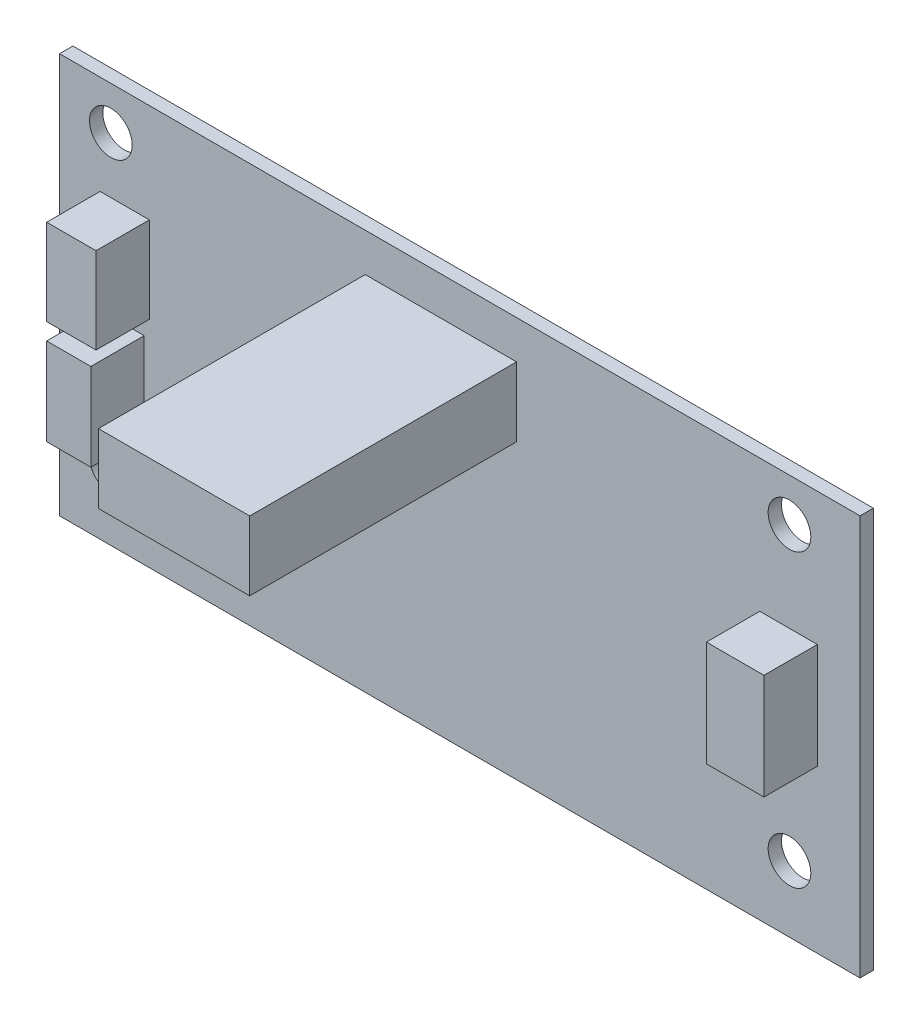
SolidWorks part; units mm, degrees
ref_plane "前视基准面" through (0, 0, 0) normal (0, 0, 1) x (1, 0, 0)
ref_plane "上视基准面" through (0, 0, 0) normal (0, 1, 0) x (1, 0, 0)
ref_plane "右视基准面" through (0, 0, 0) normal (1, 0, 0) x (0, 0, -1)
sketch "草图1" plane through (0, 0, 0) normal (0, 0, 1) x (1, 0, 0)
  line L1 (-30, 30) -> (30, 30)
  line L2 (-30, 30) -> (-30, 0)
  line L3 (-30, 0) -> (30, 0)
  line L4 (30, 30) -> (30, 0)
  dimension "D1" = 60
  dimension "D2" = 30
extrude "凸台-拉伸1" add sketch "草图1" along normal blind 1
sketch "草图2" plane through (0, 0, 1) normal (0, 0, 1) x (1, 0, 0)
  circle A0 centre (-26.1558, 26.7829) radius 1.6
  circle A1 centre (-26.1558, 4.958) radius 1.6
  circle A2 centre (24.7121, 26.7829) radius 1.6
  circle A3 centre (24.7121, 4.958) radius 1.6
extrude "切除-拉伸1" cut sketch "草图2" against normal up to next contours A1
extrude "切除-拉伸2" cut sketch "草图2<3>" against normal up to next (1 mm away)
sketch "草图2<3>" plane through (0, 0, 1) normal (0, 0, 1) x (1, 0, 0) same geometry as "草图2"
sketch "草图3" plane through (0, 0, 1) normal (0, 0, 1) x (1, 0, 0)
  line L1 (-7.0857, 27.1203) -> (4.2534, 27.1203)
  line L2 (-7.0857, 27.1203) -> (-7.0857, 21.934)
  line L3 (-7.0857, 21.934) -> (4.2534, 21.934)
  line L4 (4.2534, 27.1203) -> (4.2534, 21.934)
extrude "凸台-拉伸2" add sketch "草图3" along normal blind 20
sketch "草图5" plane through (0, 0, 0) normal (0, 0, 1) x (1, 0, 0)
  line L1 (-26.9626, 22.5792) -> (-23.2685, 22.5792)
  line L2 (-26.9626, 22.5792) -> (-26.9626, 16.1252)
  line L3 (-26.9626, 16.1252) -> (-23.2685, 16.1252)
  line L4 (-23.2685, 22.5792) -> (-23.2685, 16.1252)
  line L5 (-26.9678, 14.8705) -> (-23.6559, 14.8705)
  line L6 (-26.9678, 14.8705) -> (-26.9678, 8.3315)
  line L7 (-26.9678, 8.3315) -> (-23.6559, 8.3315)
  line L8 (-23.6559, 14.8705) -> (-23.6559, 8.3315)
  line L9 (22.4889, 20.0495) -> (26.7978, 20.0495)
  line L10 (22.4889, 20.0495) -> (22.4889, 12.1445)
  line L11 (22.4889, 12.1445) -> (26.7978, 12.1445)
  line L12 (26.7978, 20.0495) -> (26.7978, 12.1445)
extrude "凸台-拉伸3" add sketch "草图5" along normal blind 5
